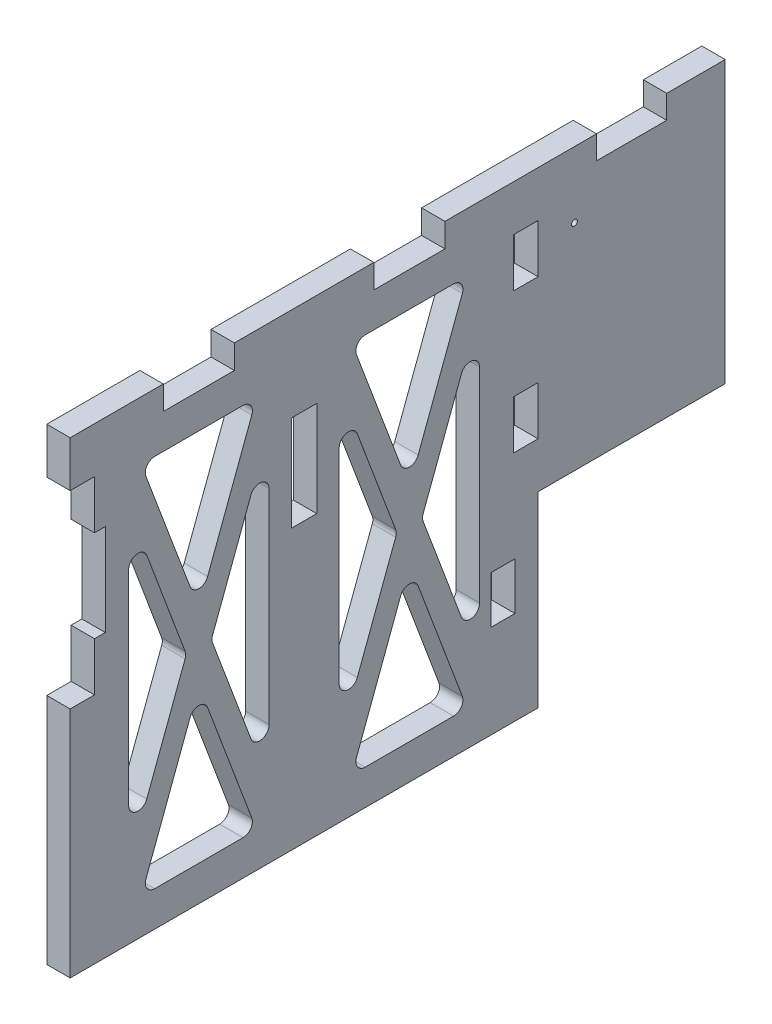
SolidWorks part; units mm, degrees
ref_plane "Front Plane" through (0, 0, 0) normal (0, 0, 1) x (1, 0, 0)
ref_plane "Top Plane" through (0, 0, 0) normal (0, 1, 0) x (1, 0, 0)
ref_plane "Right Plane" through (0, 0, 0) normal (1, 0, 0) x (0, 0, -1)
sketch "Sketch4" plane through (0, 0, 0) normal (1, 0, 0) x (0, 0, -1)
  line L0 (-3.175, 0) -> (-63.5, 0)
  line L3 (-3.175, 0) -> (3.175, 0) construction
  line L5 (3.175, 0) -> (63.5, 0)
  line L6 (63.5, 0) -> (63.5, -2.8758)
  line L7 (63.5, 127) -> (38.227, 127)
  line L8 (-63.5, 127) -> (-63.5, 114.554)
  line L9 (0, 0) -> (0, 177.7936) construction
  line L10 (-3.429, 101.6) -> (3.429, 101.6)
  line L11 (-3.175, 101.346) -> (3.175, 101.346) construction
  line L12 (-3.175, 101.346) -> (-3.175, 75.946) construction
  line L13 (-3.175, 75.946) -> (3.175, 75.946) construction
  line L14 (3.175, 101.346) -> (3.175, 75.946) construction
  line L15 (3.429, 101.6) -> (3.429, 75.692)
  line L16 (-3.429, 75.692) -> (3.429, 75.692)
  line L17 (-3.429, 101.6) -> (-3.429, 75.692)
  line L18 (-63.5, 63.5) -> (-57.15, 63.5) construction
  line L19 (-57.15, 63.5) -> (-57.15, 76.2) construction
  line L20 (-57.15, 76.2) -> (-63.5, 76.2) construction
  line L21 (-63.5, 101.6) -> (-57.15, 101.6) construction
  line L22 (-57.15, 101.6) -> (-57.15, 114.3) construction
  line L23 (-57.15, 114.3) -> (-63.5, 114.3) construction
  line L24 (-63.5, 101.346) -> (-63.5, 76.454)
  line L25 (-63.5, 63.246) -> (-63.5, 3.4742)
  line L32 (63.5, 114.554) -> (63.5, 127)
  line L34 (-63.5, 101.346) -> (-56.896, 101.346)
  line L35 (-56.896, 101.346) -> (-56.896, 114.554)
  line L36 (-56.896, 114.554) -> (-63.5, 114.554)
  line L37 (-63.5, 63.246) -> (-56.896, 63.246)
  line L38 (-56.896, 63.246) -> (-56.896, 76.454)
  line L39 (-56.896, 76.454) -> (-63.5, 76.454)
  line L40 (57.15, 114.3) -> (63.5, 114.3) construction
  line L41 (57.15, 101.6) -> (57.15, 114.3) construction
  line L42 (63.5, 101.6) -> (57.15, 101.6) construction
  line L43 (57.15, 76.2) -> (63.5, 76.2) construction
  line L44 (57.15, 63.5) -> (57.15, 76.2) construction
  line L45 (63.5, 63.5) -> (57.15, 63.5) construction
  line L46 (56.896, 76.454) -> (63.5, 76.454)
  line L47 (56.896, 63.246) -> (56.896, 76.454)
  line L48 (63.5, 63.246) -> (56.896, 63.246)
  line L49 (56.896, 114.554) -> (63.5, 114.554)
  line L50 (56.896, 101.346) -> (56.896, 114.554)
  line L51 (63.5, 101.346) -> (56.896, 101.346)
  line L52 (63.5, 101.346) -> (63.5, 76.454)
  line L53 (-18.923, 127) -> (-18.923, 120.523)
  line L59 (-19.05, 127) -> (-19.05, 120.65) construction
  line L60 (-19.05, 120.65) -> (-38.1, 120.65) construction
  line L61 (-38.1, 127) -> (-38.1, 120.65) construction
  line L62 (-18.923, 120.523) -> (-38.227, 120.523)
  line L63 (-38.227, 127) -> (-38.227, 120.523)
  line L64 (38.227, 127) -> (38.227, 120.523)
  line L65 (18.923, 120.523) -> (38.227, 120.523)
  line L66 (18.923, 127) -> (18.923, 120.523)
  line L67 (18.923, 127) -> (-18.923, 127)
  line L68 (-38.227, 127) -> (-63.5, 127)
  line L69 (63.5, 9.8242) -> (63.5, -2.8758)
  line L70 (50.8, 38.1) -> (50.8, 25.4) construction
  line L71 (57.15, 25.4) -> (50.8, 25.4) construction
  line L72 (57.15, 38.1) -> (57.15, 25.4) construction
  line L73 (-57.2262, 38.1762) -> (-50.7238, 38.1762) construction
  line L74 (-57.15, 38.1) -> (-50.8, 38.1) construction
  line L75 (-57.15, 38.1) -> (-57.15, 25.4) construction
  line L76 (0, 32.258) -> (6.35, 32.258) construction
  line L77 (57.15, 38.1) -> (50.8, 38.1) construction
  line L78 (57.2262, 38.1762) -> (57.2262, 25.3238)
  line L79 (57.2262, 25.3238) -> (50.7238, 25.3238)
  line L80 (-57.15, 25.4) -> (-50.8, 25.4) construction
  line L81 (-50.8, 38.1) -> (-50.8, 25.4) construction
  line L82 (-50.7238, 38.1762) -> (-50.7238, 25.3238) construction
  line L83 (-0.254, 32.512) -> (6.604, 32.512)
  line L84 (-63.5, -9.2258) -> (-63.5, 0)
  line L85 (63.5, 9.8242) -> (63.5, 63.246)
  line L86 (-63.5, 3.4742) -> (-63.5, -9.2258)
  line L87 (-57.2262, 25.3238) -> (-50.7238, 25.3238) construction
  line L88 (-57.2262, 38.1762) -> (-57.2262, 25.3238) construction
  line L89 (50.7238, 38.1762) -> (50.7238, 25.3238)
  line L90 (57.2262, 38.1762) -> (50.7238, 38.1762)
  line L91 (-3.175, 0) -> (3.175, 0)
  dimension "D3" = 60.325
  dimension "D4" = 127
  dimension "D5" = 6.35
  dimension "D6" = 25.4
  dimension "D8" = 25.4
  dimension "D9" = 12.7
  dimension "D10" = 12.7
  dimension "D11" = 6.35
  dimension "D12" = 25.4
  dimension "D15" = 25.4
  dimension "D16" = 19.05
  dimension "D17" = 6.35
  dimension "D19" = 6.35
  dimension "D20" = 12.7
  dimension "D21" = 25.4
  dimension "D22" = 6.35
  dimension "D24" = 127
  dimension "D7" = 0.254
  dimension "D13" = 0.254
  dimension "D14" = 0.254
  dimension "D18" = 0.127
  dimension "D23" = 0.0762
extrude "Boss-Extrude1" add sketch "Sketch4" along normal blind 6.35 contours L85 L48 L47 L46 L52 L51 L50 L49 L32 L7 L64 L65 L66 L67 L53 L62 L63 L68 L8 L36 L35 L34 L24 L39 L38 L37 L25 L73 L84 L0 L5 L6 L78 L17 L10 L15 L16 region at (0, 61.8138, 0.2954)
sketch "Sketch5" plane through (6.35, 0, 0) normal (1, 0, 0) x (0, 0, -1)
  line L1 (-47.625, 111.125) -> (47.625, 111.125)
  line L2 (-47.625, 111.125) -> (-47.625, 9.525)
  line L3 (-47.625, 9.525) -> (47.625, 9.525)
  line L4 (47.625, 111.125) -> (47.625, 9.525)
  line L8 (0, 111.125) -> (0, 9.525) construction
  line L10 (-9.525, 111.125) -> (-9.525, 9.525)
  line L12 (9.525, 111.125) -> (9.525, 9.525)
  line L13 (9.525, 9.525) -> (47.625, 111.125) construction
  line L14 (6.5522, 10.6398) -> (44.6522, 112.2398)
  line L15 (12.4978, 8.4102) -> (50.5978, 110.0102)
  line L16 (47.625, 9.525) -> (9.525, 111.125) construction
  line L17 (44.6522, 8.4102) -> (6.5522, 110.0102)
  line L18 (50.5978, 10.6398) -> (12.4978, 112.2398)
  line L19 (-9.525, 9.525) -> (-47.625, 111.125) construction
  line L20 (-6.5522, 10.6398) -> (-44.6522, 112.2398)
  line L21 (-12.4978, 8.4102) -> (-50.5978, 110.0102)
  line L22 (-47.625, 9.525) -> (-9.525, 111.125) construction
  line L23 (-44.6522, 8.4102) -> (-6.5522, 110.0102)
  line L24 (-50.5978, 10.6398) -> (-12.4978, 112.2398)
  line L25 (63.5, 0) -> (63.5, 63.246) construction
  line L26 (63.5, 127) -> (38.227, 127) construction
  line L27 (-63.5, 63.246) -> (-63.5, 0) construction
  line L28 (63.5, 0) -> (-63.5, 0) construction
  arc A0 (6.5522, 10.6398) -> (12.4978, 8.4102) centre (9.525, 9.525) ccw
  arc A1 (50.5978, 110.0102) -> (44.6522, 112.2398) centre (47.625, 111.125) ccw
  arc A2 (44.6522, 8.4102) -> (50.5978, 10.6398) centre (47.625, 9.525) ccw
  arc A3 (12.4978, 112.2398) -> (6.5522, 110.0102) centre (9.525, 111.125) ccw
  arc A4 (-6.5522, 10.6398) -> (-12.4978, 8.4102) centre (-9.525, 9.525) cw
  arc A5 (-50.5978, 110.0102) -> (-44.6522, 112.2398) centre (-47.625, 111.125) cw
  arc A6 (-44.6522, 8.4102) -> (-50.5978, 10.6398) centre (-47.625, 9.525) cw
  arc A7 (-12.4978, 112.2398) -> (-6.5522, 110.0102) centre (-9.525, 111.125) cw
  point P18 (28.575, 60.325)
  point P23 (28.575, 60.325)
  point P28 (-28.575, 60.325)
  point P33 (-28.575, 60.325)
  dimension "D6" = 3.175
  dimension "D1" = 15.875
  dimension "D2" = 15.875
  dimension "D3" = 15.875
  dimension "D4" = 9.525
  dimension "D5" = 19.05
extrude "Cut-Extrude1" cut sketch "Sketch5" against normal through all contours L2 L24 L21 | L20 L24 L1 | L23 L3 L21 | L14 L17 L12 | L18 L14 L1 | L18 L4 L15 | L3 L17 L15 | L23 L20 L10 region at (6.35, 97.2058, 28.575) region at (6.35, 60.325, 42.4053) region at (6.35, 60.325, 14.7447) region at (6.35, 23.4442, 28.575) region at (6.35, 97.2058, -28.575) region at (6.35, 60.325, -14.7447) region at (6.35, 60.325, -42.4053) region at (6.35, 23.4442, -28.575)
fillet "Fillet1" radius 2.54 24 edges at (3.175, 51.2826, 28.575) (3.175, 9.525, 12.9159) (3.175, 9.525, 44.2341) (3.175, 102.0826, 9.525) (3.175, 18.5674, 9.525) (3.175, 60.325, 25.1841) (3.175, 51.2826, -28.575) (3.175, 9.525, -44.2341) (3.175, 9.525, -12.9159) (3.175, 60.325, -31.9659) (3.175, 102.0826, -47.625) (3.175, 18.5674, -47.625) (3.175, 60.325, 31.9659) (3.175, 18.5674, 47.625) (3.175, 102.0826, 47.625) (3.175, 111.125, -12.9159) (3.175, 111.125, -44.2341) (3.175, 69.3674, -28.575) (3.175, 111.125, 12.9159) (3.175, 69.3674, 28.575) (3.175, 102.0826, -9.525) (3.175, 60.325, -25.1841) (3.175, 18.5674, -9.525) (3.175, 111.125, 44.2341)
fillet "Fillet2" [suppressed] radius 2.54
ref_plane "Plane1" through (0, 88.0753, -47.625) normal (0, -1, 0) x (-1, 0, 0)
sketch "Sketch7" plane through (0, 0, 0) normal (-1, 0, 0) x (0, 0, 1)
  line L0 (-63.5, 114.554) -> (-63.5, 127) construction
  line L1 (-63.5, 127) -> (-114.3, 127)
  line L2 (-63.5, 127) -> (-63.5, 50.8)
  line L3 (-63.5, 50.8) -> (-114.3, 50.8)
  line L4 (-114.3, 127) -> (-114.3, 50.8)
  line L5 (-63.5, 127) -> (-38.227, 127) construction
  line L6 (-88.9, 127) -> (-88.9, 106.193) construction
  line L7 (-98.425, 127) -> (-79.375, 127)
  line L8 (-98.425, 127) -> (-98.425, 120.65)
  line L9 (-98.425, 120.65) -> (-79.375, 120.65)
  line L10 (-79.375, 127) -> (-79.375, 120.65)
  dimension "D1" = 50.8
  dimension "D2" = 76.2
  dimension "D3" = 6.35
  dimension "D4" = 19.05
extrude "Boss-Extrude2" add sketch "Sketch7" against normal blind 6.35 contours L1 L10 L9 L8 L4 L3 L2 region at (0, 87.7734, -88.9)
sketch "Sketch8" plane through (6.35, 0, 0) normal (1, 0, 0) x (0, 0, -1)
  circle A0 centre (73.37, 109.0918) radius 0.7937
  dimension "D1" = 1.5875
extrude "Cut-Extrude2" cut sketch "Sketch8" against normal through all
sketch "Sketch9" plane through (6.35, 0, 0) normal (1, 0, 0) x (0, 0, -1)
  line L0 (-56.896, 76.454) -> (-63.5, 76.454) construction
  line L1 (-63.5, 101.346) -> (-53.975, 101.346)
  line L2 (-63.5, 101.346) -> (-63.5, 76.454)
  line L3 (-63.5, 76.454) -> (-53.975, 76.454)
  line L4 (-53.975, 101.346) -> (-53.975, 76.454)
  dimension "D1" = 9.525
extrude "Cut-Extrude3" cut sketch "Sketch9" against normal through all both and the other way through all
